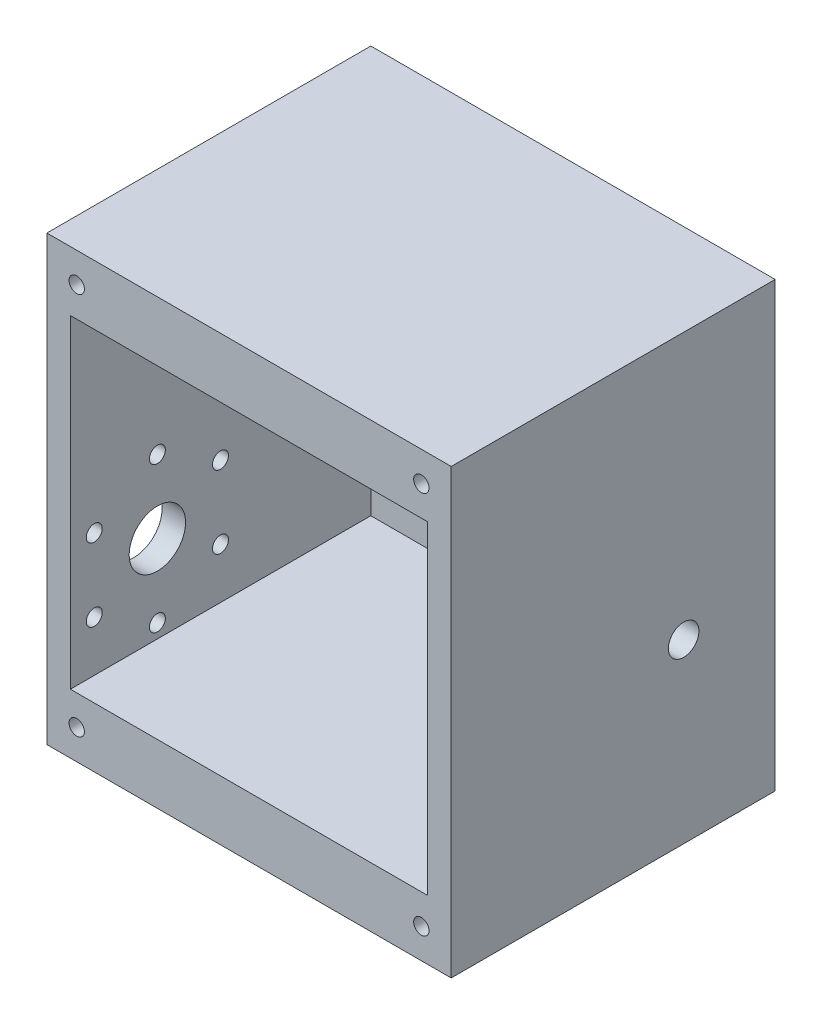
SolidWorks part; units mm, degrees
ref_plane "Front" through (0, 0, 0) normal (0, 0, 1) x (1, 0, 0)
ref_plane "Top" through (0, 0, 0) normal (0, 1, 0) x (1, 0, 0)
ref_plane "Right" through (0, 0, 0) normal (1, 0, 0) x (0, 0, -1)
sketch "Sketch1" plane through (0, 0, 0) normal (0, 0, 1) x (1, 0, 0)
  line L1 (-43, -47.117) -> (43, -47.117)
  line L2 (-43, -47.117) -> (-43, 47.117)
  line L3 (-43, 47.117) -> (43, 47.117)
  line L4 (43, -47.117) -> (43, 47.117)
  line L5 (-43, -47.117) -> (43, 47.117) construction
  line L6 (-43, 47.117) -> (43, -47.117) construction
  point P0 (0, 0)
  dimension "D1" = 86
  dimension "D2" = 94.234
extrude "Boss-Extrude1" add sketch "Sketch1" along normal blind 68.9031
sketch "Sketch2" plane through (0, 0, 68.9031) normal (0, 0, 1) x (1, 0, 0)
  line L0 (43, 47.117) -> (-43, 47.117) construction
  line L1 (-38, -34.417) -> (38, -34.417)
  line L2 (-38, -34.417) -> (-38, 34.417)
  line L3 (-38, 34.417) -> (38, 34.417)
  line L4 (38, -34.417) -> (38, 34.417)
  line L5 (-38, -34.417) -> (38, 34.417) construction
  line L6 (-38, 34.417) -> (38, -34.417) construction
  line L7 (-43, 47.117) -> (-43, -47.117) construction
  point P0 (0, 0)
  dimension "D1" = 12.7
  dimension "D2" = 5
extrude "Cut-Extrude1" cut sketch "Sketch2" against normal offset from surface (63.9031 mm away) 5 up to face at (0, 0, 0)
sketch "Sketch3" plane through (0, 0, 5) normal (0, 0, 1) x (1, 0, 0)
  line L0 (38, 34.417) -> (-38, 34.417) construction
  line L1 (-11.276, 34.417) -> (-3.656, 34.417)
  line L2 (-11.276, 34.417) -> (-11.276, 26.797)
  line L3 (-11.276, 26.797) -> (-3.656, 26.797)
  line L4 (-3.656, 34.417) -> (-3.656, 26.797)
  line L5 (30.38, 34.417) -> (38, 34.417)
  line L6 (30.38, 34.417) -> (30.38, 26.797)
  line L7 (30.38, 26.797) -> (38, 26.797)
  line L8 (38, 34.417) -> (38, 26.797)
  line L9 (-11.276, -14.097) -> (-3.656, -14.097)
  line L10 (-11.276, -14.097) -> (-11.276, -21.717)
  line L11 (-11.276, -21.717) -> (-3.656, -21.717)
  line L12 (-3.656, -14.097) -> (-3.656, -21.717)
  line L13 (30.38, -14.097) -> (38, -14.097)
  line L14 (30.38, -14.097) -> (30.38, -21.717)
  line L15 (30.38, -21.717) -> (38, -21.717)
  line L16 (38, -14.097) -> (38, -21.717)
  line L17 (38, -34.417) -> (38, 34.417) construction
  dimension "D1" = 7.62
  dimension "D2" = 49.276
  dimension "D3" = 56.134
extrude "Boss-Extrude2" add sketch "Sketch3" along normal blind 6.35
hole_wizard "#4-40 Tapped Hole1" positions "Sketch6" profile "Sketch7" tap size "#4-40" standard "ANSI Inch"
sketch "Sketch6" plane through (0, 0, 11.35) normal (0, 0, 1) x (1, 0, 0)
  line L1 (-3.656, 34.417) -> (-11.276, 34.417) construction
  line L2 (-11.276, 34.417) -> (-11.276, 26.797) construction
  line L3 (38, 34.417) -> (30.38, 34.417) construction
  line L4 (30.38, 34.417) -> (30.38, 26.797) construction
  line L5 (-3.656, -14.097) -> (-11.276, -14.097) construction
  line L6 (-11.276, -14.097) -> (-11.276, -21.717) construction
  line L7 (38, -14.097) -> (30.38, -14.097) construction
  line L8 (30.38, -14.097) -> (30.38, -21.717) construction
  point P0 (-7.466, 30.607)
  point P2 (34.19, 30.607)
  point P4 (-7.466, -17.907)
  point P6 (34.19, -17.907)
  point P16 (-7.466, 34.417)
  point P20 (-11.276, 30.607)
  point P24 (34.19, 34.417)
  point P28 (30.38, 30.607)
  point P32 (-7.466, -14.097)
  point P36 (-11.276, -17.907)
  point P40 (34.19, -14.097)
  point P44 (30.38, -17.907)
sketch "Sketch7" plane through (-7.466, 30.607, 11.35) normal (1, 0, 0) x (0, -1, 0)
  line L0 (0, 0) -> (0, 5.429)
  line L1 (0, 5.429) -> (1.1303, 4.7498)
  line L2 (1.1303, 4.7498) -> (1.1303, 0)
  line L5 (1.1303, 0) -> (0, 0)
  line L10 (0, 5.429) -> (-1.1303, 4.7498) construction
  line L11 (0, -6.35) -> (0, 107.95) construction
  dimension "Tap Drill Dia." = 2.2606
  dimension "Tap Drill Depth" = 4.7498
  dimension "Drill Angle" = 118
cosmetic thread "Hole Thread1" parameters "D1"=5.588, "D2"=2.8448
cosmetic thread "Hole Thread2" parameters "D1"=5.588, "D2"=2.8448
cosmetic thread "Hole Thread3" parameters "D1"=5.588, "D2"=2.8448
cosmetic thread "Hole Thread4" parameters "D1"=5.588, "D2"=2.8448
hole_wizard "Ø6.5 (6.5) Diameter Hole1" positions "Sketch8" profile "Sketch9" hole size "Ø6.5" standard "ANSI Metric" end condition up to next
sketch "Sketch8" plane through (43, 0, 0) normal (1, 0, 0) x (0, 0, -1)
  line L0 (-11.35, -21.717) -> (-5, -21.717) construction
  line L1 (-11.35, -21.717) -> (-11.35, -14.097) construction
  point P0 (-19.4502, -9.525)
  dimension "D1" = 12.192
  dimension "D2" = 8.1002
sketch "Sketch9" plane through (43, -9.525, 19.4502) normal (0, 1, 0) x (0, 0, -1)
  line L0 (0, 0) -> (0, 5)
  line L1 (0, 5) -> (3.25, 5)
  line L2 (3.25, 5) -> (3.25, 0)
  line L5 (3.25, 0) -> (0, 0)
  line L11 (0, -6.35) -> (0, 107.95) construction
  dimension "Thru Hole Dia." = 6.5
  dimension "Thru Hole Depth" = 5
sketch "Sketch10" plane through (-43, 0, 0) normal (-1, 0, 0) x (0, 0, 1)
  line L0 (5, -34.417) -> (68.9031, -34.417) construction
  line L1 (68.9031, 34.417) -> (68.9031, -34.417) construction
  point P0 (50.4031, -15.917)
  dimension "D1" = 18.5
  dimension "D2" = 18.5
hole_wizard "Ø12.0 (12) Diameter Hole1" positions "Sketch11" profile "Sketch12" hole size "Ø12.0" standard "ANSI Metric" end condition up to next
sketch "Sketch11" plane through (-43, 0, 0) normal (-1, 0, 0) x (0, 0, 1)
  point P0 (50.4031, -15.917)
sketch "Sketch12" plane through (-43, -15.917, 50.4031) normal (0, 1, 0) x (0, 0, 1)
  line L0 (0, 0) -> (0, 5)
  line L1 (0, 5) -> (6, 5)
  line L2 (6, 5) -> (6, 0)
  line L5 (6, 0) -> (0, 0)
  line L11 (0, -6.35) -> (0, 107.95) construction
  dimension "Thru Hole Dia." = 12
  dimension "Thru Hole Depth" = 5
hole_wizard "CSK for M3 Flat Head Machine Screw1" positions "Sketch13" profile "Sketch14" countersink size "M3" standard "ANSI Metric" end condition up to next
sketch "Sketch13" plane through (-43, 0, 0) normal (-1, 0, 0) x (0, 0, 1)
  line L0 (50.4031, -15.917) -> (50.4031, -0.417) construction
  point P0 (50.4031, -0.417)
  point P10 (63.8265, -8.167)
  point P11 (63.8265, -23.667)
  point P12 (50.4031, -31.417)
  point P13 (36.9797, -23.667)
  point P14 (36.9797, -8.167)
  dimension "D1" = 15.5
  dimension "D3" = 15.5
sketch "Sketch14" plane through (-43, -0.417, 50.4031) normal (0, 1, 0) x (0, 0, 1)
  line L0 (0, 0) -> (0, 5)
  line L1 (0, 5) -> (1.7, 5)
  line L2 (1.7, 5) -> (1.7, 1.45)
  line L3 (1.7, 1.45) -> (3.15, 0)
  line L5 (3.15, 0) -> (0, 0)
  line L6 (-1.7, 1.45) -> (-3.15, 0) construction
  line L11 (0, -6.35) -> (0, 107.95) construction
  dimension "Thru Hole Dia." = 3.4
  dimension "Thru Hole Depth" = 5
  dimension "Near C'Sink Dia." = 6.3
  dimension "Near C'Sink Angle" = 90
hole_wizard "#4 Clearance Hole1" positions "Sketch15" profile "Sketch16" hole size "#4" standard "ANSI Inch" end condition up to next
sketch "Sketch15" plane through (0, 0, 68.9031) normal (0, 0, 1) x (1, 0, 0)
  line L0 (43, 47.117) -> (-43, 47.117) construction
  line L1 (-43, 47.117) -> (-43, -47.117) construction
  line L2 (43, -47.117) -> (43, 47.117) construction
  line L3 (-43, -47.117) -> (43, -47.117) construction
  point P0 (-36.65, 40.767)
  point P2 (36.65, 40.767)
  point P4 (-36.65, -40.767)
  point P6 (36.65, -40.767)
  dimension "D1" = 6.35
  dimension "D2" = 6.35
  dimension "D3" = 6.35
  dimension "D4" = 6.35
sketch "Sketch16" plane through (-36.65, 40.767, 68.9031) normal (1, 0, 0) x (0, -1, 0)
  line L0 (0, 0) -> (0, 68.9031)
  line L1 (0, 68.9031) -> (1.6319, 68.9031)
  line L2 (1.6319, 68.9031) -> (1.6319, 0)
  line L5 (1.6319, 0) -> (0, 0)
  line L11 (0, -6.35) -> (0, 107.95) construction
  dimension "Thru Hole Dia." = 3.2639
  dimension "Thru Hole Depth" = 68.9031
equation "\"PCB Width\"= 1940mil"
equation "\"PCB Height\"= 2210mil"
equation "\"PCB Thickness\"= 63mil"
equation "\"Motor Body Front Diameter\"= 37mm"
equation "\"Motor Body Front Length\"= 30mm"
equation "\"Motor Bearing Length\"= 5mm"
equation "\"Motor Body Back Length\"= 33.3mm"
equation "\"Large PVC Fittings Wall Thickness\"= 15in / 64"
equation "\"Large PVC Pipe Outer Diameter\"= 3.5in"
equation "\"Box Width\"= 2 * \"Motor Bearing Length\" + \"Motor Body Front Length\" + \"Motor Body Back Length\" + 0.5in"
equation "\"Box Hole Center to Edge Distance\"= 250mil"
equation "\"Box Ceiling and Floor Thickness\"= 2 * \"Box Hole Center to Edge Distance\""
equation "\"Box Height\"= 2 * \"Box Ceiling and Floor Thickness\" + \"PCB Height\" + 0.5in"
equation "\"Box Back Depth\"= \"Large PVC Fittings Wall Thickness\" + \"Large PVC Pipe Outer Diameter\" / 2 + \"Motor Body Front Diameter\" / 2"
equation "\"D1@Sketch1\"=\"Box Width\""
equation "\"D2@Sketch1\"=\"Box Height\""
equation "\"D1@Boss-Extrude1\"=\"Box Back Depth\""
equation "\"D1@Sketch2\"=\"Box Ceiling and Floor Thickness\""
equation "\"D2@Sketch2\"=\"Motor Bearing Length\""
equation "\"D1@Cut-Extrude1\"=\"Motor Bearing Length\""
equation "\"D2@Sketch3\"=\"PCB Width\""
equation "\"D3@Sketch3\"=\"PCB Height\""
equation "\"Tap Drill Depth@Sketch7\"=0.25in - \"PCB Thickness\""
equation "\"D2@Sketch8\"=\"PCB Thickness\" + 6.5mm"
equation "\"Motor Body Front Radius\"= \"Motor Body Front Diameter\" / 2"
equation "\"D1@Sketch10\"=\"Motor Body Front Radius\""
equation "\"D2@Sketch10\"=\"Motor Body Front Radius\""
equation "\"Motor PCR\"= 31mm / 2"
equation "\"D1@Sketch13\"=\"Motor PCR\""
equation "\"D1@Sketch15\"=\"Box Hole Center to Edge Distance\""
equation "\"D2@Sketch15\"=\"Box Hole Center to Edge Distance\""
equation "\"D3@Sketch15\"=\"Box Hole Center to Edge Distance\""
equation "\"D4@Sketch15\"=\"Box Hole Center to Edge Distance\""
